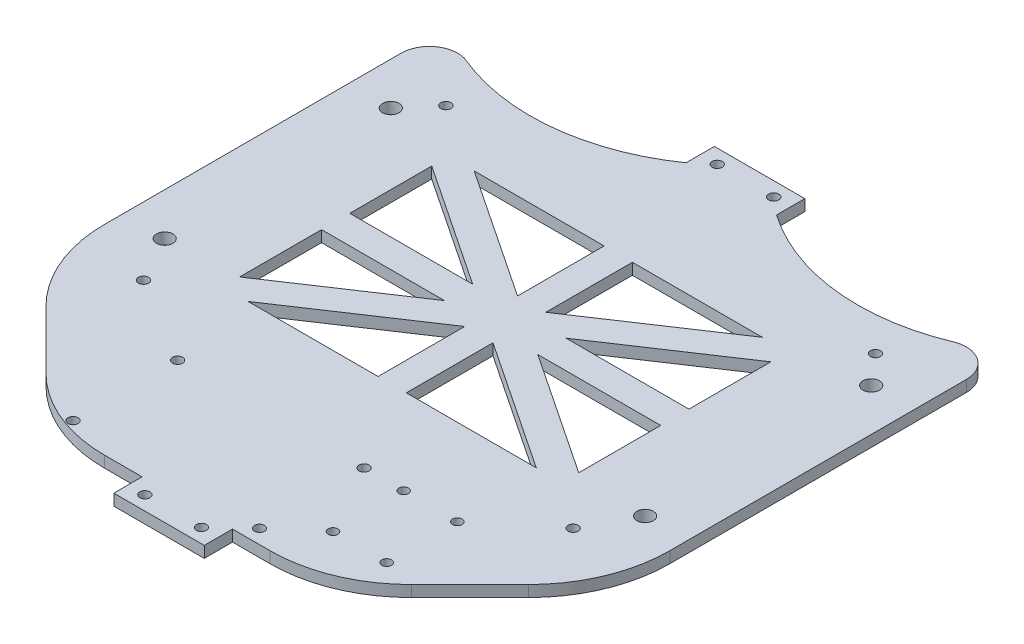
SolidWorks part; units mm, degrees
material "PLA"
ref_plane "Front Plane" through (0, 0, 0) normal (0, 0, 1) x (1, 0, 0)
ref_plane "Top Plane" through (0, 0, 0) normal (0, 1, 0) x (1, 0, 0)
ref_plane "Right Plane" through (0, 0, 0) normal (1, 0, 0) x (0, 0, -1)
sketch "Sketch1" plane through (0, 0, 0) normal (0, 1, 0) x (1, 0, 0)
  line L0 (-100, -222) -> (100, -222)
  line L1 (100, -222) -> (100, -29.5)
  line L2 (100, -29.5) -> (16, -29.5) construction
  line L3 (16, -29.5) -> (16, -19.5)
  line L10 (-16, -29.5) -> (-100, -29.5) construction
  line L11 (-100, -29.5) -> (-100, -222)
  line L12 (0, -222) -> (0, 5.5) construction
  line L17 (-10, -24.5) -> (10, -24.5) construction
  line L18 (-16, -29.5) -> (16, -29.5) construction
  line L19 (-10, -227) -> (10, -227) construction
  line L20 (-16.5139, -104.5) -> (-60, -104.5)
  line L21 (-60, -114.5) -> (-16.5139, -114.5)
  line L22 (-5, -118.8426) -> (-5, -149.5)
  line L27 (5, -118.8426) -> (5, -149.5)
  line L28 (60, -109.5) -> (-60, -109.5) construction
  line L29 (60, -114.5) -> (16.5139, -114.5)
  line L30 (16.5139, -104.5) -> (60, -104.5)
  line L31 (5, -100.1574) -> (5, -69.5)
  line L32 (-5, -100.1574) -> (-5, -69.5)
  line L54 (-60, -69.5) -> (-60, -149.5)
  line L55 (-60, -149.5) -> (60, -149.5)
  line L56 (60, -149.5) -> (60, -69.5)
  line L57 (60, -69.5) -> (-60, -69.5)
  line L59 (-16, -19.5) -> (16, -19.5)
  line L61 (-16, -222) -> (-16, -232)
  line L62 (-16, -232) -> (16, -232)
  line L63 (16, -232) -> (16, -222)
  line L64 (17, -183) -> (17, -210)
  line L65 (17, -210) -> (-18, -210)
  line L66 (-18, -210) -> (-18, -183)
  line L67 (-18, -183) -> (17, -183)
  line L68 (-45.45, -217) -> (-45.45, -180) construction
  line L69 (-45.45, -180) -> (20.55, -180) construction
  line L70 (20.55, -180) -> (20.55, -217) construction
  line L74 (-60, -75.5093) -> (50.9861, -149.5)
  line L75 (60, -143.4907) -> (-50.9861, -69.5)
  line L76 (-60, -143.4907) -> (50.9861, -69.5)
  line L77 (-50.9861, -149.5) -> (60, -75.5093)
  line L78 (60, -69.5) -> (-60, -149.5) construction
  line L79 (-60, -69.5) -> (60, -149.5) construction
  line L81 (-16, -19.5) -> (-16, -29.5)
  arc A11 (16, -29.5) -> (100, -29.5) centre (58, 30.5) ccw
  arc A12 (-16, -29.5) -> (-100, -29.5) centre (-58, 30.5) cw
  point P5 (-76, -161.5)
  point P6 (-76, -54.5)
  point P7 (76, -161.5)
  point P8 (76, -54.5)
  point P10 (-10, -24.5)
  point P11 (10, -24.5)
  point P12 (0, -222)
  point P27 (0, -109.5)
  point P37 (0, -109.5)
  point P45 (0, 0)
  point P46 (0, 0)
  point P53 (0, -232)
  point P58 (-45.45, -180)
  point P59 (-45.45, -217)
  point P60 (20.55, -180)
  point P62 (20.55, -217)
  point P131 (-85, -65)
  point P132 (-85, -145)
  point P133 (85, -145)
  point P134 (85, -65)
  dimension "D29" = 22
  dimension "D30" = 10
  dimension "D31" = 27
  dimension "D39" = 3
  dimension "D12" = 152
  dimension "D13" = 60
  dimension "D4" = 200
  dimension "D8" = 30.5
  dimension "D9" = 192.5
  dimension "D10" = 10
  dimension "D11" = 16
  dimension "D14" = 107
  dimension "D15" = 25
  dimension "D16" = 20
  dimension "D17" = 5
  dimension "D18" = 20
  dimension "D19" = 40
  dimension "D20" = 10
  dimension "D21" = 10
  dimension "D22" = 20.55
  dimension "D32" = 35
  dimension "D33" = 17
  dimension "D37" = 37
  dimension "D38" = 66
  dimension "D58" = 120
  dimension "D60" = 80
  dimension "D67" = 80
  dimension "D68" = 170
  dimension "D69" = 77
  dimension "D75" = 10
  dimension "D76" = 10
extrude "Boss-Extrude1" add sketch "Sketch1" along normal blind 4 contours L12 | L12 | A12 L11 L0 L1 A11 L3 L57 L56 L55 L54 | L74 L76 L75 L57 L54 | L74 L77 L75 L76 | L77 L74 L55 L56 L75 | L55 L77 L74 L76 L54 | L75 L77 L56 L57 L76 | L62 L63 L0 L61 | L21 L76 L74 L20 L54 | L75 L76 L31 L57 L32 | L77 L75 L29 L56 L30 | L77 L22 L55 L27 L74 | L67 L66 L65 L64 region at (-97.1538, 0, 125.75) region at (0, 0, 227) region at (-36.3323, 0, 109.5) region at (-31.1426, 0, 88.7382) region at (0, 0, 109.5) region at (-31.1426, 0, 130.2618) region at (31.1426, 0, 130.2618) region at (0, 0, 133.3236) region at (31.1426, 0, 88.7382) region at (0, 0, 85.6764) region at (36.3323, 0, 109.5) region at (-0.5, 0, 196.5)
hole_wizard "M5 Clearance Hole1" positions "Sketch15" profile "Sketch14" hole size "M5" standard "ISO" end condition through all
sketch "Sketch15" plane through (0, 4, 0) normal (0, 1, 0) x (1, 0, 0)
  point P0 (-85, -65)
  point P3 (-85, -145)
  point P6 (85, -145)
  point P9 (85, -65)
sketch "Sketch14" plane through (-85, 4, 65) normal (1, 0, 0) x (0, 0, 1)
  line L0 (0, 0) -> (0, 4)
  line L1 (0, 4) -> (2.9, 4)
  line L2 (2.9, 4) -> (2.9, 0)
  line L5 (2.9, 0) -> (0, 0)
  line L11 (0, -6.35) -> (0, 107.95) construction
  dimension "Thru Hole Dia." = 5.8
  dimension "Thru Hole Depth" = 4
fillet "Fillet1" radius 10 2 edges at (100, 2, 29.5) (-100, 2, 29.5)
hole_wizard "M3 Clearance Hole1" positions "Sketch16" profile "Sketch17" hole size "M3" standard "ISO"
sketch "Sketch16" plane through (0, 4, 0) normal (0, 1, 0) x (1, 0, 0)
  point P0 (-45.45, -217)
  point P3 (-45.45, -180)
  point P6 (20.55, -180)
  point P9 (20.55, -217)
sketch "Sketch17" plane through (-45.45, 4, 217) normal (1, 0, 0) x (0, 0, 1)
  line L0 (0, 0) -> (0, 11.0815)
  line L1 (0, 11.0815) -> (1.8, 10)
  line L2 (1.8, 10) -> (1.8, 0)
  line L5 (1.8, 0) -> (0, 0)
  line L10 (0, 11.0815) -> (-1.8, 10) construction
  line L11 (0, -6.35) -> (0, 107.95) construction
  dimension "Hole Dia." = 3.6
  dimension "Hole Depth" = 10
  dimension "Drill Angle" = 118
chamfer "Chamfer1" distance 50 angle 45 2 edges at (100, 2, 222) (-100, 2, 222)
fillet "Fillet3" radius 50 4 edges at (-100, 2, 172) (-50, 2, 222) (100, 2, 172) (50, 2, 222)
hole_wizard "M3 Clearance Hole2" positions "Sketch18" profile "Sketch19" hole size "M3" standard "ISO" end condition through all
sketch "Sketch18" plane through (0, 4, 0) normal (0, 1, 0) x (1, 0, 0)
  point P0 (-76, -54.5)
  point P3 (76, -54.5)
  point P6 (76, -161.5)
  point P9 (-76, -161.5)
  point P12 (-10, -24.5)
  point P15 (10, -24.5)
  point P19 (-10, -227)
  point P22 (10, -227)
sketch "Sketch19" plane through (-76, 4, 54.5) normal (1, 0, 0) x (0, 0, 1)
  line L0 (0, 0) -> (0, 4)
  line L1 (0, 4) -> (1.8, 4)
  line L2 (1.8, 4) -> (1.8, 0)
  line L5 (1.8, 0) -> (0, 0)
  line L11 (0, -6.35) -> (0, 107.95) construction
  dimension "Thru Hole Dia." = 3.6
  dimension "Thru Hole Depth" = 4
sketch "Sketch20" plane through (0, 4, 0) normal (0, 1, 0) x (1, 0, 0)
  line L0 (16, -222) -> (29.2893, -222) construction
  line L1 (53.55, -180) -> (34.55, -180) construction
  line L2 (53.55, -180) -> (53.55, -205) construction
  line L3 (53.55, -205) -> (34.55, -205) construction
  line L4 (34.55, -180) -> (34.55, -205) construction
  line L5 (53.55, -180) -> (34.55, -205) construction
  line L6 (53.55, -205) -> (34.55, -180) construction
  circle A0 centre (20.55, -217) radius 1.8 construction
  point P0 (44.05, -192.5)
  dimension "D1" = 25
  dimension "D2" = 19
  dimension "D3" = 17
  dimension "D4" = 14
hole_wizard "M3 Clearance Hole3" positions "Sketch23" profile "Sketch24" hole size "M3" standard "ISO" end condition through all
sketch "Sketch23" plane through (0, 4, 0) normal (0, 1, 0) x (1, 0, 0)
  point P0 (53.55, -180)
  point P3 (34.55, -180)
  point P6 (34.55, -205)
  point P9 (53.55, -205)
sketch "Sketch24" plane through (53.55, 4, 180) normal (1, 0, 0) x (0, 0, 1)
  line L0 (0, 0) -> (0, 4)
  line L1 (0, 4) -> (1.7, 4)
  line L2 (1.7, 4) -> (1.7, 0)
  line L5 (1.7, 0) -> (0, 0)
  line L11 (0, -6.35) -> (0, 107.95) construction
  dimension "Thru Hole Dia." = 3.4
  dimension "Thru Hole Depth" = 4
equation "\"w9\"=2"
